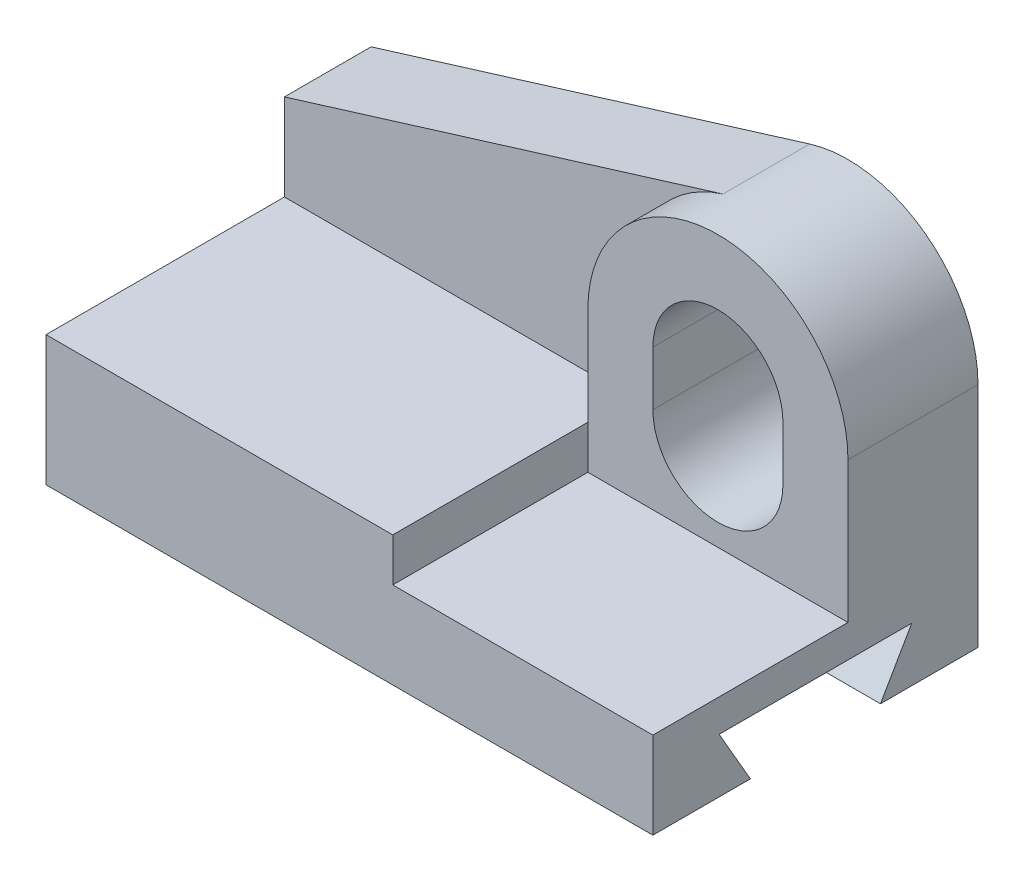
SolidWorks part; units mm, degrees
ref_plane "前视基准面" through (0, 0, 0) normal (0, 0, 1) x (1, 0, 0)
ref_plane "上视基准面" through (0, 0, 0) normal (0, 1, 0) x (1, 0, 0)
ref_plane "右视基准面" through (0, 0, 0) normal (1, 0, 0) x (0, 0, -1)
other "Configuration Table"
sketch "草图1" plane through (0, 0, 0) normal (0, 0, 1) x (1, 0, 0)
  line L0 (0, 0) -> (56, 0)
  line L1 (56, 0) -> (56, 21)
  line L2 (32, 8) -> (32, 21)
  line L3 (0, 12) -> (32, 12)
  line L4 (0, 0) -> (0, 20)
  line L5 (32, 8) -> (56, 8)
  line L6 (0, 20) -> (40.4666, 32.468)
  line L7 (44, 21) -> (44, 16) construction
  line L8 (50, 21) -> (50, 16)
  line L9 (38, 21) -> (38, 16)
  arc A0 (56, 21) -> (32, 21) centre (44, 21) ccw
  arc A1 (50, 21) -> (38, 21) centre (44, 21) ccw
  arc A2 (38, 16) -> (50, 16) centre (44, 16) ccw
  point P13 (44, 18.5)
  dimension "D7" = 6
  dimension "D2" = 12
  dimension "D1" = 56
  dimension "D3" = 20
  dimension "D4" = 12
  dimension "D5" = 8
  dimension "D6" = 13
  dimension "D8" = 5
extrude "凸台-拉伸1" add sketch "草图1" along normal blind 30 contours L5 L2 L3 L4 L0 L1 region at (25.3333, 5.3333, 0)
extrude "凸台-拉伸2" add sketch "草图1<4>" along normal blind 8 contours A0 L6 L4 L3 L2 region at (18.5762, 19.113, 0)
sketch "草图1<4>" plane through (0, 0, 0) normal (0, 0, 1) x (1, 0, 0) same geometry as "草图1"
extrude "凸台-拉伸3" add sketch "草图1<5>" along normal blind 12 contours L1 A0 L2 L5 A2 L9 A1 L8 region at (44, 8.3466, 0)
sketch "草图1<5>" plane through (0, 0, 0) normal (0, 0, 1) x (1, 0, 0) same geometry as "草图1"
sketch "草图5" plane through (0, 0, 0) normal (-1, 0, 0) x (0, 0, 1)
  line L0 (15, 0) -> (15, 30.9482) construction
  line L1 (30, 0) -> (0, 0) construction
  line L2 (9, 0) -> (6.1132, 5)
  line L3 (6.1132, 5) -> (23.8868, 5)
  line L4 (9, 0) -> (21, 0)
  line L5 (21, 0) -> (23.8868, 5)
  point P9 (15, 5)
  dimension "D1" = 6
  dimension "D2" = 5
  dimension "D3" = 60
extrude "切除-拉伸1" cut sketch "草图5" against normal through all
